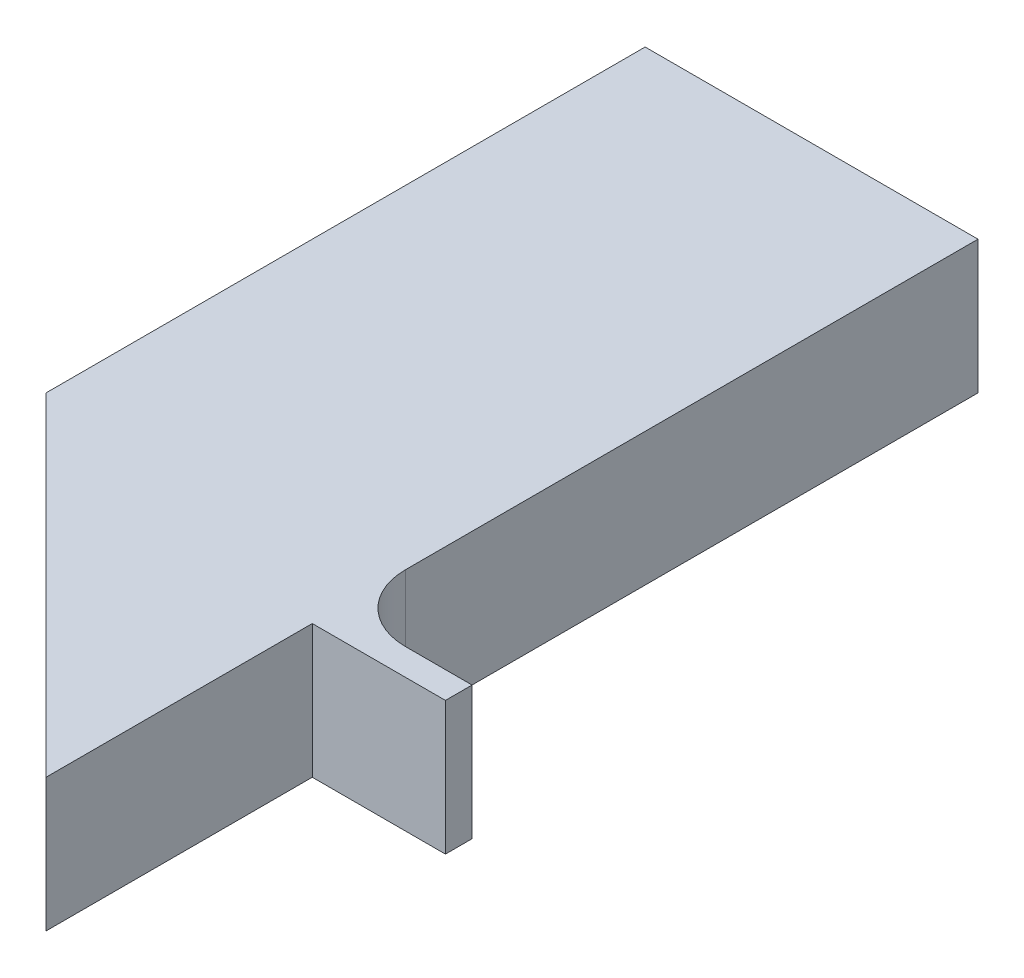
SolidWorks part; units mm, degrees
ref_plane "Front Plane" through (0, 0, 0) normal (0, 0, 1) x (1, 0, 0)
ref_plane "Top Plane" through (0, 0, 0) normal (0, 1, 0) x (1, 0, 0)
ref_plane "Right Plane" through (0, 0, 0) normal (1, 0, 0) x (0, 0, -1)
sketch "Sketch1" plane through (0, 0, 0) normal (0, 1, 0) x (1, 0, 0)
  line L0 (-50, 50) -> (0, 0)
  line L1 (-50, 140) -> (0, 140)
  line L2 (-50, 140) -> (-50, 50)
  line L4 (0, 140) -> (0, 0)
  dimension "D1" = 50
  dimension "D2" = 45
  dimension "D3" = 140
extrude "Boss-Extrude1" add sketch "Sketch1" along normal blind 20
sketch "Sketch2" plane through (0, 0, 0) normal (1, 0, 0) x (0, 0, -1)
  line L0 (0, 20) -> (140, 20) construction
  line L1 (40, 20) -> (44, 20)
  line L2 (40, 20) -> (40, 0)
  line L3 (40, 0) -> (44, 0)
  line L4 (44, 20) -> (44, 0)
  line L5 (0, 0) -> (140, 0) construction
  line L6 (0, 20) -> (0, 0) construction
  dimension "D1" = 40
  dimension "D2" = 4
extrude "Boss-Extrude2" add sketch "Sketch2" along normal blind 20
sketch "Sketch3" plane through (-50, 0, 0) normal (-1, 0, 0) x (0, 0, 1)
  line L0 (0, 20) -> (0, 0) construction
  line L1 (-46, 16) -> (0, 16)
  line L2 (-46, 16) -> (-46, 4)
  line L3 (-46, 4) -> (0, 4)
  line L4 (0, 16) -> (0, 4)
  line L5 (-50, 20) -> (0, 20) construction
  line L6 (-50, 0) -> (0, 0) construction
  line L7 (-50, 20) -> (-50, 0) construction
  dimension "D1" = 4
  dimension "D2" = 4
  dimension "D3" = 4
extrude "Cut-Extrude1" cut sketch "Sketch3" against normal offset from surface (46 mm away) 4 up to face at (0, 10, -20)
sketch "Sketch4" plane through (0, 0, 0) normal (0, -1, 0) x (1, 0, 0)
  line L0 (-36, -140) -> (-36, -36) construction
  line L3 (20, -44) -> (0, -44) construction
  line L4 (0, -140) -> (-50, -140) construction
  line L5 (-50, -50) -> (0, 0) construction
  line L6 (-50, -140) -> (-50, -50) construction
  circle A0 centre (-36, -59) radius 11
  circle A1 centre (-36, -119) radius 11
  point P4 (-25, -137.3966)
  point P7 (0, 0)
  point P8 (-40.8818, -140)
  point P11 (-38.3602, -38.3602)
  dimension "D1" = 22
  dimension "D2" = 22
  dimension "D3" = 15
  dimension "D4" = 60
  dimension "D5" = 14
extrude "Cut-Extrude2" cut sketch "Sketch4" against normal blind 8
fillet "Fillet1" radius 10 1 edges at (0, 10, -44)
